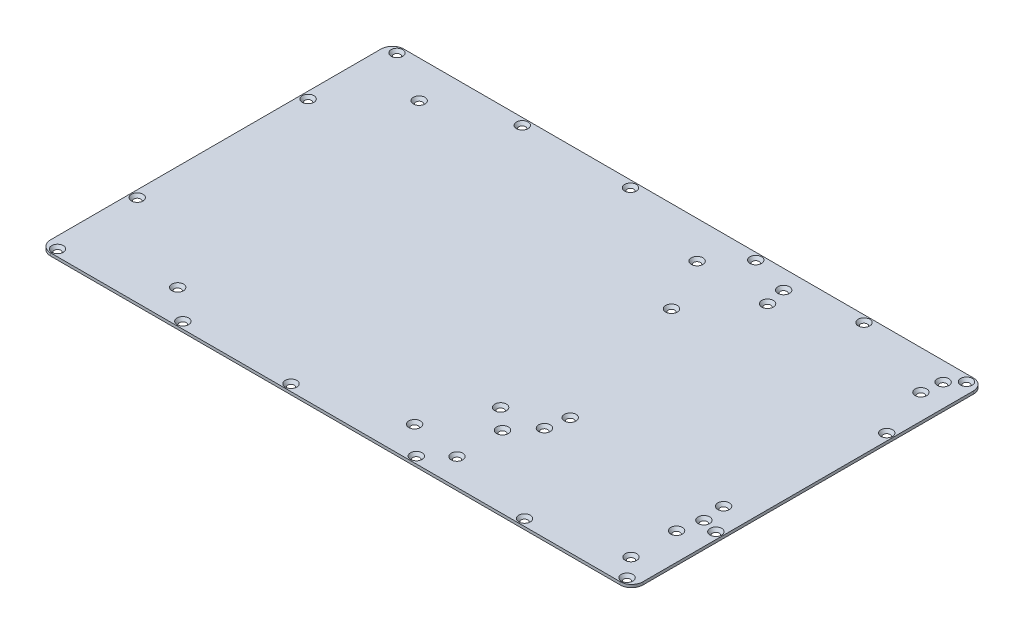
SolidWorks part; units mm, degrees
material "5052-H32"
ref_plane "Front Plane" through (0, 0, 0) normal (0, 0, 1) x (1, 0, 0)
ref_plane "Top Plane" through (0, 0, 0) normal (0, 1, 0) x (1, 0, 0)
ref_plane "Right Plane" through (0, 0, 0) normal (1, 0, 0) x (0, 0, -1)
sketch "Sketch1" plane through (0, 0, 0) normal (0, 1, 0) x (1, 0, 0)
  line L1 (-165.1, -98.425) -> (165.1, -98.425)
  line L2 (-165.1, -98.425) -> (-165.1, 98.425)
  line L3 (-165.1, 98.425) -> (165.1, 98.425)
  line L4 (165.1, -98.425) -> (165.1, 98.425)
  line L5 (-165.1, -98.425) -> (165.1, 98.425) construction
  line L6 (-165.1, 98.425) -> (165.1, -98.425) construction
  point P0 (0, 0)
  dimension "D1" = 330.2
  dimension "D2" = 196.85
extrude "Boss-Extrude1" add sketch "Sketch1" along normal blind 1.5875
fillet "Fillet1" radius 6.35 4 edges at (-165.1, 0.7937, 98.425) (-165.1, 0.7937, -98.425) (165.1, 0.7937, -98.425) (165.1, 0.7937, 98.425)
hole_wizard "CSK for #4 Flat Head Socket Cap Screw1" positions "Sketch3" profile "Sketch2" countersink size "#4" standard "Ansi Inch" end condition through all
sketch "Sketch3" plane through (0, 1.5875, 0) normal (0, 1, 0) x (-1, 0, 0)
  line L0 (-165.1, 92.075) -> (-165.1, -92.075) construction
  line L1 (-158.75, -98.425) -> (158.75, -98.425) construction
  line L2 (158.75, 98.425) -> (-158.75, 98.425) construction
  point P0 (-161.29, 47.625)
  point P1 (-161.29, -47.625)
  dimension "D1" = 3.81
  dimension "D2" = 50.8
  dimension "D3" = 50.8
sketch "Sketch2" plane through (161.29, 1.5875, 47.625) normal (1, 0, 0) x (0, 0, 1)
  line L0 (0, 0) -> (0, 1.5875)
  line L1 (0, 1.5875) -> (1.632, 1.5875)
  line L2 (1.632, 1.5875) -> (1.6319, 1.8481)
  line L3 (1.6319, 1.8481) -> (3.2385, 0)
  line L5 (3.2385, 0) -> (0, 0)
  line L6 (-1.6319, 1.8481) -> (-3.2385, 0) construction
  line L11 (0, -6.35) -> (0, 107.95) construction
  dimension "Thru Hole Dia." = 3.2639
  dimension "Thru Hole Depth" = 1.5875
  dimension "Near C'Sink Dia." = 6.477
  dimension "Near C'Sink Angle" = 82
pattern_linear "LPattern1" count 2 spacing 120.015 along (-1, 0, 0) of "CSK for #4 Flat Head Socket Cap Screw1"
mirror "Mirror1" about plane through (0, 0, 0) normal (1, 0, 0) of "CSK for #4 Flat Head Socket Cap Screw1"
hole_wizard "CSK for #4 Flat Head Socket Cap Screw2" positions "Sketch6" profile "Sketch7" countersink size "#4" standard "Ansi Inch" end condition through all
sketch "Sketch6" plane through (0, 1.5875, 0) normal (0, 1, 0) x (-1, 0, 0)
  line L0 (-171.823, 94.615) -> (176.2442, 94.615) construction
  line L2 (158.75, 98.425) -> (-158.75, 98.425) construction
  line L3 (-165.1, 92.075) -> (-165.1, -92.075) construction
  point P0 (-158.75, 94.615)
  point P7 (-101.6, 94.615)
  point P9 (-41.275, 94.615)
  point P11 (28.575, 94.615)
  point P13 (88.9, 94.615)
  point P15 (158.75, 94.615)
  dimension "D1" = 3.81
  dimension "D2" = 6.35
  dimension "D3" = 57.15
  dimension "D4" = 117.475
  dimension "D5" = 69.85
  dimension "D6" = 200.025
  dimension "D7" = 69.85
sketch "Sketch7" plane through (158.75, 1.5875, 94.615) normal (1, 0, 0) x (0, 0, 1)
  line L0 (0, 0) -> (0, 1.5875)
  line L1 (0, 1.5875) -> (1.632, 1.5875)
  line L2 (1.632, 1.5875) -> (1.6319, 1.8481)
  line L3 (1.6319, 1.8481) -> (3.2385, 0)
  line L5 (3.2385, 0) -> (0, 0)
  line L6 (-1.6319, 1.8481) -> (-3.2385, 0) construction
  line L11 (0, -6.35) -> (0, 107.95) construction
  dimension "Thru Hole Dia." = 3.2639
  dimension "Thru Hole Depth" = 1.5875
  dimension "Near C'Sink Dia." = 6.477
  dimension "Near C'Sink Angle" = 82
mirror "Mirror2" about plane through (0, 0, 0) normal (0, 0, 1) of "CSK for #4 Flat Head Socket Cap Screw2"
hole_wizard "CSK for #4 Flat Head Socket Cap Screw3" positions "Sketch10" profile "Sketch9" countersink size "#4" standard "Ansi Inch" end condition through all
sketch "Sketch10" plane through (0, 1.5875, 0) normal (0, 1, 0) x (-1, 0, 0)
  line L0 (-158.75, -98.425) -> (158.75, -98.425) construction
  line L1 (-165.1, 92.075) -> (-165.1, -92.075) construction
  point P0 (-152.4, -87.9348)
  point P1 (-63.5, -87.9348)
  point P3 (-63.5, 45.4152)
  point P5 (-152.4, 45.4152)
  dimension "D1" = 88.9
  dimension "D2" = 133.35
  dimension "D3" = 10.4902
  dimension "D4" = 12.7
sketch "Sketch9" plane through (152.4, 1.5875, -87.9348) normal (1, 0, 0) x (0, 0, 1)
  line L0 (0, 0) -> (0, 1.5875)
  line L1 (0, 1.5875) -> (1.632, 1.5875)
  line L2 (1.632, 1.5875) -> (1.6319, 1.8481)
  line L3 (1.6319, 1.8481) -> (3.2385, 0)
  line L5 (3.2385, 0) -> (0, 0)
  line L6 (-1.6319, 1.8481) -> (-3.2385, 0) construction
  line L11 (0, -6.35) -> (0, 107.95) construction
  dimension "Thru Hole Dia." = 3.2639
  dimension "Thru Hole Depth" = 1.5875
  dimension "Near C'Sink Dia." = 6.477
  dimension "Near C'Sink Angle" = 82
hole_wizard "CSK for #4 Flat Head Socket Cap Screw4" positions "Sketch12" profile "Sketch11" countersink size "#4" standard "Ansi Inch" end condition through all
sketch "Sketch12" plane through (0, 1.5875, 0) normal (0, 1, 0) x (-1, 0, 0)
  line L0 (-158.75, -98.425) -> (158.75, -98.425) construction
  line L1 (-165.1, 92.075) -> (-165.1, -92.075) construction
  point P0 (-65.6336, -76.835)
  point P1 (-151.13, -76.835)
  point P3 (-65.6336, 33.1724)
  point P5 (-151.13, 33.1724)
  dimension "D1" = 21.59
  dimension "D2" = 13.97
  dimension "D3" = 85.4964
  dimension "D4" = 110.0074
sketch "Sketch11" plane through (65.6336, 1.5875, -76.835) normal (1, 0, 0) x (0, 0, 1)
  line L0 (0, 0) -> (0, 1.5875)
  line L1 (0, 1.5875) -> (1.632, 1.5875)
  line L2 (1.632, 1.5875) -> (1.6319, 1.8481)
  line L3 (1.6319, 1.8481) -> (3.2385, 0)
  line L5 (3.2385, 0) -> (0, 0)
  line L6 (-1.6319, 1.8481) -> (-3.2385, 0) construction
  line L11 (0, -6.35) -> (0, 107.95) construction
  dimension "Thru Hole Dia." = 3.2639
  dimension "Thru Hole Depth" = 1.5875
  dimension "Near C'Sink Dia." = 6.477
  dimension "Near C'Sink Angle" = 82
hole_wizard "CSK for #4 Flat Head Socket Cap Screw5" positions "Sketch14" profile "Sketch13" countersink size "#4" standard "Ansi Inch" end condition through all
sketch "Sketch14" plane through (0, 1.5875, 0) normal (0, 1, 0) x (-1, 0, 0)
  line L0 (-165.1, 92.075) -> (-165.1, -92.075) construction
  circle A0 centre (-152.4, 45.4152) radius 1.8585 construction
  point P0 (-149.86, 58.1152)
  point P1 (-149.86, 83.5152)
  point P3 (-52.832, 58.1152)
  point P5 (-52.832, 83.5152)
  dimension "D1" = 12.7
  dimension "D2" = 97.028
  dimension "D3" = 25.4
  dimension "D4" = 15.24
sketch "Sketch13" plane through (149.86, 1.5875, 58.1152) normal (1, 0, 0) x (0, 0, 1)
  line L0 (0, 0) -> (0, 1.5875)
  line L1 (0, 1.5875) -> (1.632, 1.5875)
  line L2 (1.632, 1.5875) -> (1.6319, 1.8481)
  line L3 (1.6319, 1.8481) -> (3.2385, 0)
  line L5 (3.2385, 0) -> (0, 0)
  line L6 (-1.6319, 1.8481) -> (-3.2385, 0) construction
  line L11 (0, -6.35) -> (0, 107.95) construction
  dimension "Thru Hole Dia." = 3.2639
  dimension "Thru Hole Depth" = 1.5875
  dimension "Near C'Sink Dia." = 6.477
  dimension "Near C'Sink Angle" = 82
hole_wizard "CSK for #4 Flat Head Socket Cap Screw6" positions "Sketch16" profile "Sketch15" countersink size "#4" standard "Ansi Inch" end condition through all
sketch "Sketch16" plane through (0, 1.5875, 0) normal (0, 1, 0) x (-1, 0, 0)
  line L0 (165.1, -92.075) -> (165.1, 92.075) construction
  line L1 (-158.75, -98.425) -> (158.75, -98.425) construction
  point P0 (129.54, -77.7748)
  point P1 (-25.4, -77.7748)
  point P3 (-25.4, 79.7052)
  point P5 (106.68, 79.7052)
  dimension "D1" = 35.56
  dimension "D2" = 20.6502
  dimension "D3" = 154.94
  dimension "D4" = 157.48
  dimension "D5" = 132.08
sketch "Sketch15" plane through (-129.54, 1.5875, -77.7748) normal (1, 0, 0) x (0, 0, 1)
  line L0 (0, 0) -> (0, 1.5875)
  line L1 (0, 1.5875) -> (1.632, 1.5875)
  line L2 (1.632, 1.5875) -> (1.6319, 1.8481)
  line L3 (1.6319, 1.8481) -> (3.2385, 0)
  line L5 (3.2385, 0) -> (0, 0)
  line L6 (-1.6319, 1.8481) -> (-3.2385, 0) construction
  line L11 (0, -6.35) -> (0, 107.95) construction
  dimension "Thru Hole Dia." = 3.2639
  dimension "Thru Hole Depth" = 1.5875
  dimension "Near C'Sink Dia." = 6.477
  dimension "Near C'Sink Angle" = 82
